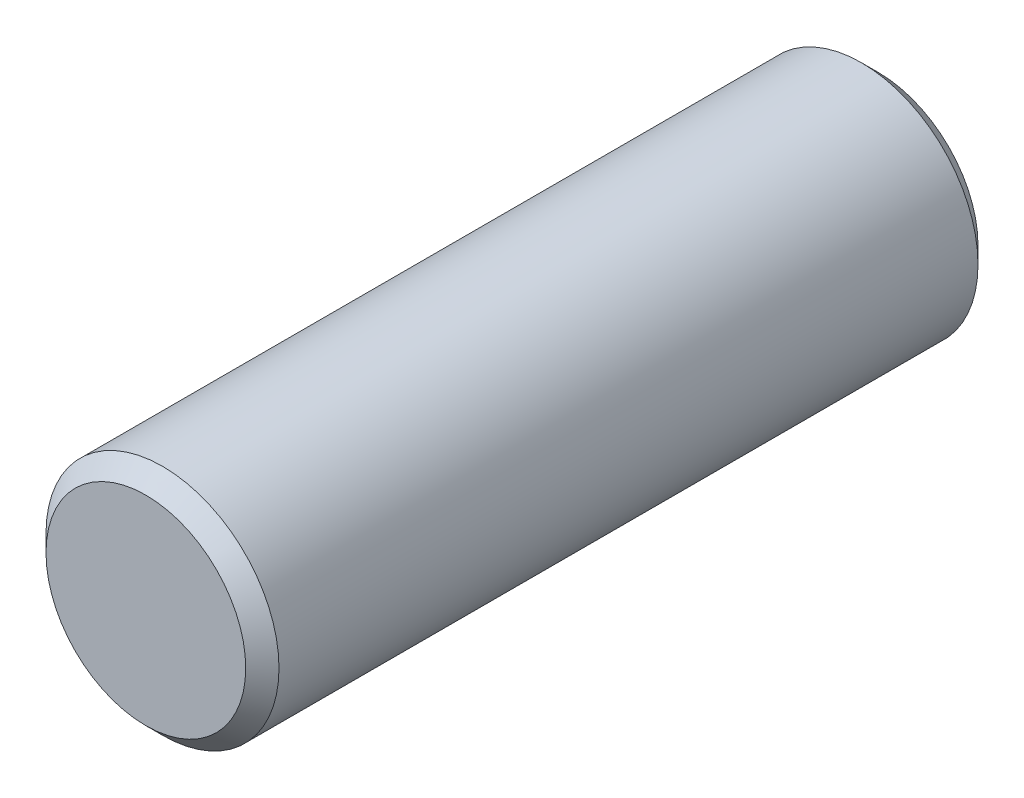
SolidWorks part; units mm, degrees
note: '?' marks a value the reader was unsure of.
ref_plane "Face" through (0, 0, 0) normal (0, 0, 1) x (1, 0, 0)
ref_plane "Dessus" through (0, 0, 0) normal (0, 1, 0) x (1, 0, 0)
ref_plane "Droite" through (0, 0, 0) normal (1, 0, 0) x (0, 0, -1)
ref_axis "Axe1" through (0, 0, -50) along (0, 0, 1)?
sketch "Esquisse1" plane through (0, 0, 0) normal (0, 0, 1) x (1, 0, 0)
  circle A0 centre (0, 0) radius 3.5
  circle A1 centre (0, 0) radius 3.5 construction
extrude "Base-Extrusion" add sketch "Esquisse1" along normal up to surface (22 mm away)
chamfer "Chanfrein1" distance 0.5 angle 45 2 edges at (3.5, 0, 0) (0, 3.5, -22)
